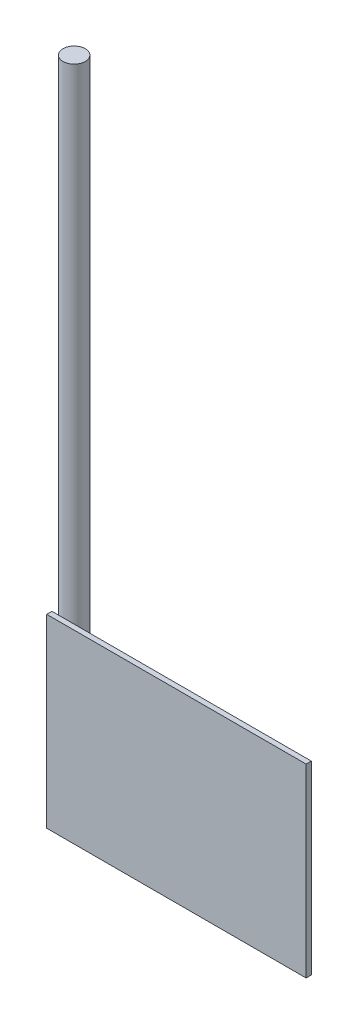
SolidWorks part; units mm, degrees
ref_plane "Front Plane" through (0, 0, 0) normal (0, 0, 1) x (1, 0, 0)
ref_plane "Top Plane" through (0, 0, 0) normal (0, 1, 0) x (1, 0, 0)
ref_plane "Right Plane" through (0, 0, 0) normal (1, 0, 0) x (0, 0, -1)
sketch "Sketch1" plane through (0, 0, 0) normal (0, 0, 1) x (1, 0, 0)
  line L1 (-17.5, 12.5) -> (17.5, 12.5)
  line L2 (-17.5, 12.5) -> (-17.5, -12.5)
  line L3 (-17.5, -12.5) -> (17.5, -12.5)
  line L4 (17.5, 12.5) -> (17.5, -12.5)
  line L5 (-17.5, 12.5) -> (17.5, -12.5) construction
  line L6 (-17.5, -12.5) -> (17.5, 12.5) construction
  point P0 (0, 0)
  dimension "D1" = 35
  dimension "D2" = 25
base flange "Base-Flange1" sketch "Sketch1" thickness 0.7 reverse thickness direction no parameters "D1"=0.5
sketch "Sketch6" plane through (0, -12.5, 0) normal (0, 1, 0) x (1, 0, 0)
  line L2 (-17.5, 0.7) -> (17.5, 0.7) construction
  circle A0 centre (-16, 2.2) radius 1.5
  dimension "D1" = 3
  dimension "D2" = 1.5
extrude "Boss-Extrude1" add sketch "Sketch6" along normal blind 90 separate body
sketch "Bend-Lines1" [suppressed] plane through (0, 0, 0) normal (0, 1, 0) x (1, 0, 0)
sketch "Bounding-Box1" [suppressed] plane through (0, 0, 0) normal (0, 1, 0) x (1, 0, 0)
sheet metal parameters "Sheet-Metal1" thickness 0.7 parameters "D1"=0.5
flat pattern "Flat-Pattern1" [suppressed]
sketch "Bend-Lines2" plane through (0, 0, 0) normal (0, 1, 0) x (1, 0, 0)
sketch3d "Bounding-Box2" [suppressed]
  line L0 (-17.5, -12.5, 0) -> (17.5, -12.5, 0) construction
  line L1 (-17.5, 12.5, 0) -> (17.5, 12.5, 0) construction
  line L2 (-17.5, -12.5, 0) -> (-17.5, 12.5, 0) construction
  line L3 (17.5, -12.5, 0) -> (17.5, 12.5, 0) construction
